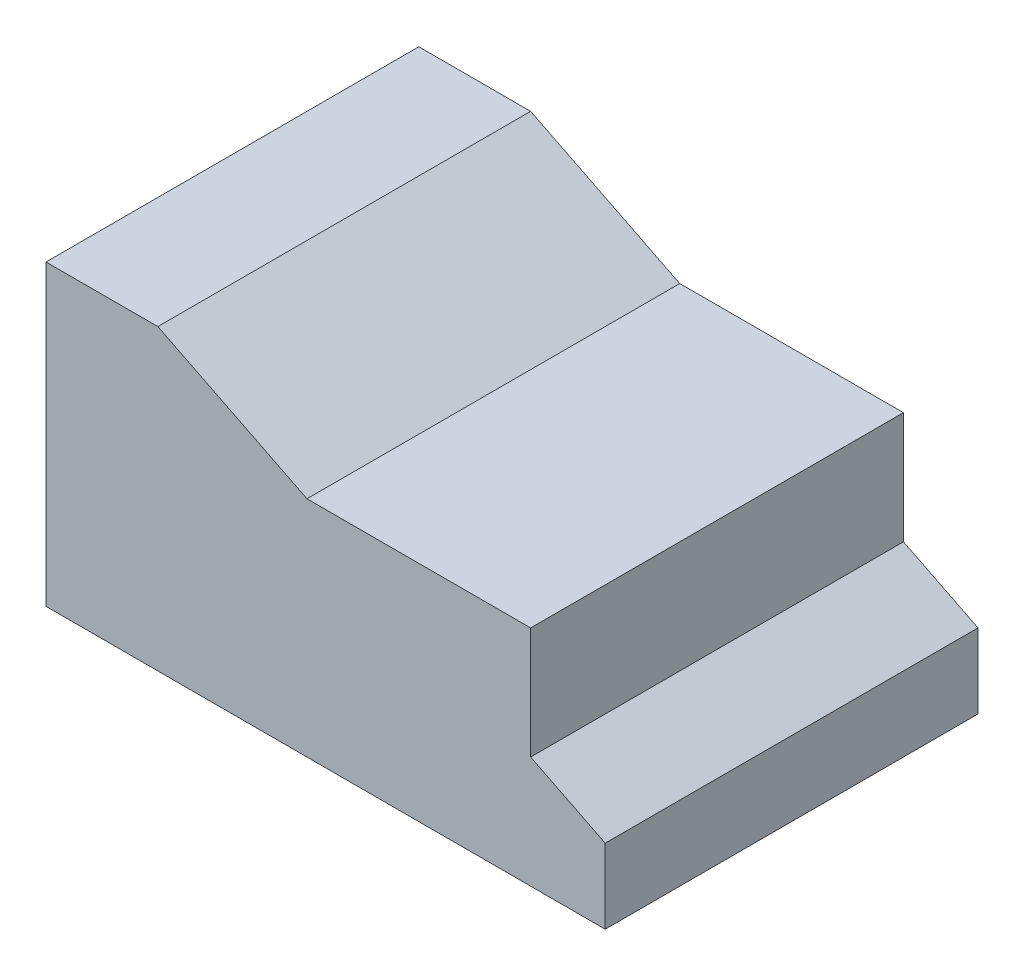
SolidWorks part; units mm, degrees
ref_plane "Front Plane" through (0, 0, 0) normal (0, 0, 1) x (1, 0, 0)
ref_plane "Top Plane" through (0, 0, 0) normal (0, 1, 0) x (1, 0, 0)
ref_plane "Right Plane" through (0, 0, 0) normal (1, 0, 0) x (0, 0, -1)
sketch "Sketch1" plane through (0, 0, 0) normal (0, 0, 1) x (1, 0, 0)
  line L0 (0, 0) -> (0, 80)
  line L1 (0, 80) -> (30, 80)
  line L2 (30, 80) -> (150, 20)
  line L3 (150, 20) -> (150, 0)
  line L4 (150, 0) -> (0, 0)
  dimension "D1" = 80
  dimension "D2" = 30
  dimension "D3" = 20
  dimension "D4" = 150
extrude "Boss-Extrude1" add sketch "Sketch1" against normal blind 100
sketch "Sketch2" plane through (0, 0, 0) normal (0, 0, 1) x (1, 0, 0)
  line L0 (150, 20) -> (30, 80) construction
  line L1 (68.7906, 60) -> (130, 60)
  line L2 (68.7906, 60) -> (68.7906, 30)
  line L3 (68.7906, 30) -> (130, 30)
  line L4 (130, 60) -> (130, 30)
  line L5 (150, 0) -> (150, 20) construction
  dimension "D1" = 20
  dimension "D2" = 30
extrude "Boss-Extrude2" add sketch "Sketch2" against normal through all
